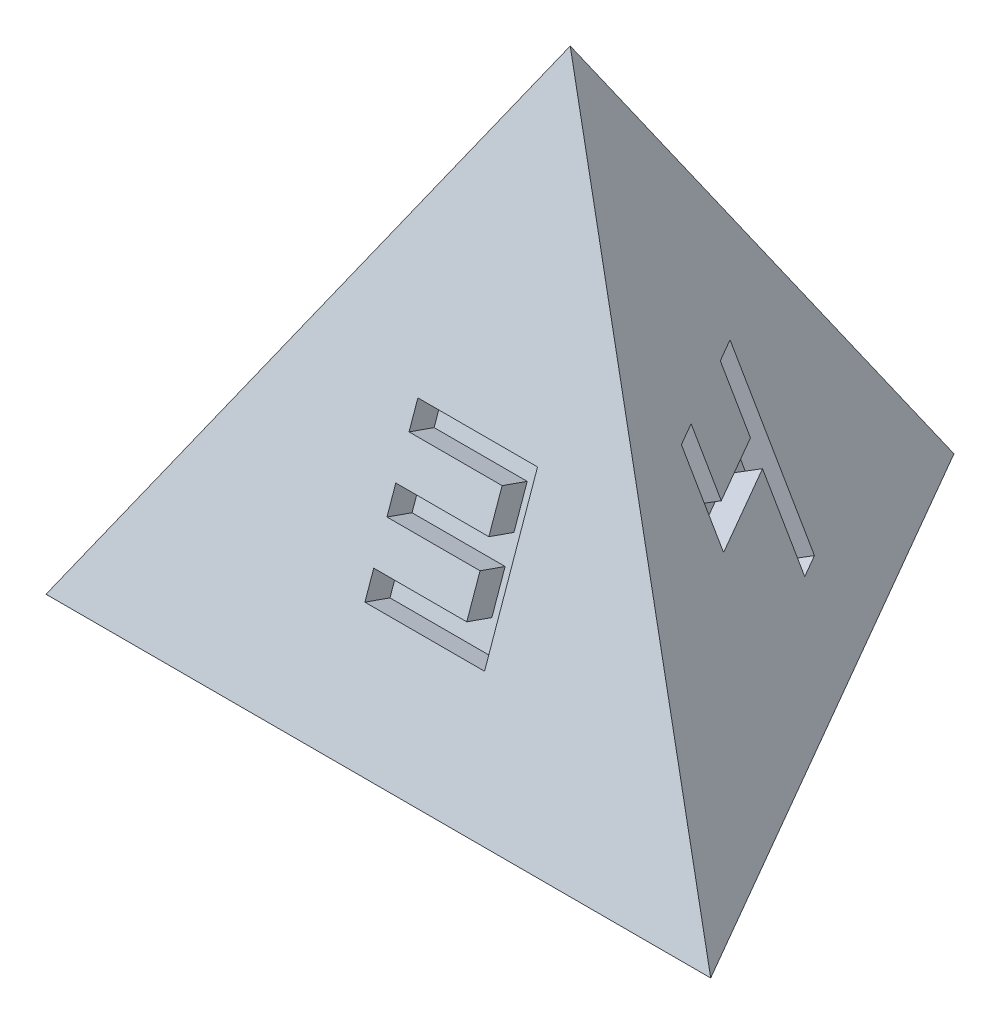
SolidWorks part; units mm, degrees
ref_plane "Front Plane" through (0, 0, 0) normal (0, 0, 1) x (1, 0, 0)
ref_plane "Top Plane" through (0, 0, 0) normal (0, 1, 0) x (1, 0, 0)
ref_plane "Right Plane" through (0, 0, 0) normal (1, 0, 0) x (0, 0, -1)
sketch "Sketch1" plane through (0, 0, 0) normal (0, 1, 0) x (1, 0, 0)
  line L1 (0, 7.3323) -> (-6.35, -3.6662)
  line L2 (-6.35, -3.6662) -> (6.35, -3.6662)
  line L3 (6.35, -3.6662) -> (0, 7.3323)
  circle A0 centre (0, 0) radius 3.6662 construction
  dimension "D1" = 12.7
ref_plane "Plane1" through (0, 10.414, 0) normal (0, 1, 0) x (1, 0, 0)
sketch "Sketch2" plane through (0, 10.414, 0) normal (0, 1, 0) x (1, 0, 0)
  point P0 (0, 0)
loft "Loft1" add profiles "Sketch2", "Sketch1"
ref_plane "Plane2" through (0, 5.334, 0) normal (0, 1, 0) x (1, 0, 0)
sketch "Sketch4" plane through (0, 1.1483, 3.2619) normal (0, 0.3321, 0.9433) x (1, 0, 0)
  line L0 (-1.016, 2.5926) -> (1.016, 2.5926)
  line L1 (1.016, 2.5926) -> (1.016, 3.8626)
  line L2 (1.016, 3.8626) -> (-1.016, 3.8626)
  line L3 (1.016, 2.5926) -> (1.016, 1.3226)
  line L4 (1.016, 1.3226) -> (-1.016, 1.3226)
  line L5 (-6.35, -1.2174) -> (6.35, -1.2174) construction
  line L6 (-6.35, -1.2174) -> (6.35, -1.2174)
  line L7 (1.27, 2.5926) -> (1.27, 4.1166)
  line L8 (1.27, 4.1166) -> (-1.016, 4.1166)
  line L9 (-1.016, 2.3386) -> (1.016, 2.3386)
  line L10 (0.762, 2.5926) -> (0.762, 1.5766)
  line L11 (0.762, 1.5766) -> (-1.016, 1.5766)
  line L12 (0.762, 2.5926) -> (0.762, 3.6086)
  line L13 (0.762, 3.6086) -> (-1.016, 3.6086)
  line L14 (-1.016, 2.8466) -> (1.016, 2.8466)
  line L15 (1.27, 2.5926) -> (1.27, 1.0686)
  line L16 (1.27, 1.0686) -> (-1.016, 1.0686)
  line L17 (-1.016, 4.1166) -> (-1.016, 3.6086)
  line L18 (-1.016, 2.8466) -> (-1.016, 2.3386)
  line L19 (-1.016, 1.5766) -> (-1.016, 1.0686)
  point P3 (0, 2.5926)
  point P10 (0, -1.2174)
  dimension "D1" = 1.27
  dimension "D2" = 2.032
  dimension "D3" = 2.54
  dimension "D4" = 0.254
  dimension "D5" = 0.254
ref_axis "Axis1" through (0, 10.414, 0) along (0, 1, 0)
extrude "Cut-Extrude1" cut sketch "Sketch4" against normal blind 0.508 contours L4 L19 L16 L15 L7 L8 L17 L2 L1 L3 | L2 L17 L13 L12 L14 L1 | L14 L12 L0 L1 | L0 L10 L9 L3 | L14 L18 L0 L12 | L0 L18 L9 L10 | L11 L19 L4 L3 L9 L10 region at (-0.127, 3.7136, 2.3588) region at (-0.127, 3.474, 2.4432) region at (0.889, 3.7136, 2.3588) region at (0.889, 3.474, 2.4432) region at (1.0541, 3.7136, 2.3588) region at (0.889, 3.3328, 2.4929) region at (0.7847, 4.1928, 2.1901)
sketch "Sketch6" plane through (2.8249, 1.1483, -1.631) normal (0.8169, 0.3321, -0.4716) x (-0.4369, -0.1776, -0.8818)
  line L0 (-1.8496, 9.6474) -> (0.2292, -1.1956) construction
  line L2 (-6.0072, -2.3913) -> (6.4656, 0) construction
  line L3 (-1.486, 2.3549) -> (0.5097, 2.7375)
  line L4 (-1.486, 2.3549) -> (-1.7729, 3.8517)
  line L5 (0.5097, 2.7375) -> (0.2227, 4.2343)
  line L6 (0.5097, 2.7375) -> (0.8923, 0.7419)
  line L7 (-1.2844, 2.6522) -> (0.4618, 2.987)
  line L8 (-1.2844, 2.6522) -> (-1.5235, 3.8995)
  line L9 (0.7591, 2.7853) -> (0.4722, 4.2821)
  line L10 (0.2602, 2.6897) -> (0.6428, 0.694)
  line L11 (-1.6876, 2.0576) -> (0.5575, 2.4881)
  line L12 (-1.6876, 2.0576) -> (-2.0224, 3.8038)
  line L13 (0.2602, 2.6897) -> (-0.0267, 4.1864)
  line L14 (0.7591, 2.7853) -> (1.1417, 0.7897)
  line L15 (-2.0224, 3.8038) -> (-1.5235, 3.8995)
  line L16 (-0.0267, 4.1864) -> (0.4722, 4.2821)
  line L17 (1.1417, 0.7897) -> (0.6428, 0.694)
  point P9 (-0.4882, 2.5462)
  dimension "D1" = 1.524
  dimension "D2" = 2.032
  dimension "D3" = 2.032
  dimension "D4" = 3.81
  dimension "D5" = 0.254
  dimension "D6" = 0.254
extrude "Cut-Extrude2" cut sketch "Sketch6" against normal blind 0.508 contours L0 L3 L4 L15 L12 L11 | L0 L7 L8 L15 L4 L3 | L7 L0 L3 L13 | L3 L0 L11 L10 | L13 L3 L5 L7 | L10 L11 L6 L3 | L16 L13 L7 L5 | L17 L14 L9 L16 L5 L6 | L17 L6 L11 L10 region at (1.8523, 3.7136, -1.5094) region at (2.0529, 3.7136, -1.162) region at (1.9254, 3.474, -1.5515) region at (2.1278, 3.474, -1.2009) region at (1.3792, 4.4324, -1.8228) region at (1.5983, 3.7136, -1.9493) region at (1.6714, 3.474, -1.9915) region at (1.5809, 3.3542, -2.2325) region at (1.9635, 2.5157, -2.1602)
sketch "Sketch7" plane through (-2.8249, 1.1483, -1.631) normal (-0.8169, 0.3321, -0.4716) x (-0.4369, 0.1776, 0.8818)
  line L0 (1.8496, 9.6474) -> (-0.2292, -1.1956) construction
  line L1 (-6.4656, 0) -> (6.0072, -2.3913) construction
  line L2 (-0.3184, 3.7353) -> (1.6773, 3.3527)
  line L3 (-0.5575, 2.4881) -> (1.4382, 2.1055)
  line L4 (-0.7966, 1.2408) -> (1.199, 0.8582)
  line L5 (-0.3184, 3.7353) -> (-0.5575, 2.4881)
  line L6 (1.4382, 2.1055) -> (1.199, 0.8582)
  line L7 (-0.8444, 0.9913) -> (1.4007, 0.5609)
  line L8 (1.7354, 2.3071) -> (1.4007, 0.5609)
  line L9 (-0.2602, 2.6897) -> (1.7354, 2.3071)
  line L10 (-0.1167, 3.4381) -> (-0.2602, 2.6897)
  line L11 (-0.1167, 3.4381) -> (1.6295, 3.1033)
  line L12 (-0.7488, 1.4902) -> (0.9974, 1.1555)
  line L13 (1.1409, 1.9038) -> (0.9974, 1.1555)
  line L14 (-0.8548, 2.2864) -> (1.1409, 1.9038)
  line L15 (-0.52, 4.0326) -> (-0.8548, 2.2864)
  line L16 (-0.52, 4.0326) -> (1.7251, 3.6022)
  line L17 (1.7251, 3.6022) -> (1.6295, 3.1033)
  line L18 (-0.7488, 1.4902) -> (-0.8444, 0.9913)
  point P8 (0.6795, 3.544)
  point P11 (0.4403, 2.2968)
  point P14 (0.2012, 1.0495)
  dimension "D1" = 2.032
  dimension "D2" = 1.27
  dimension "D3" = 1.27
  dimension "D4" = 2.286
  dimension "D5" = 0.254
  dimension "D6" = 0.254
extrude "Cut-Extrude3" cut sketch "Sketch7" against normal blind 0.508 contours L0 L2 L5 L3 L9 L10 L11 | L0 L16 L15 L14 L3 L5 L2 | L16 L0 L2 L17 | L2 L0 L11 L17 | L9 L0 L3 L6 L4 L7 L8 | L3 L0 L14 L13 L12 L4 L6 | L0 L12 L18 L4 | L0 L4 L18 L7 region at (-2.0046, 4.6719, -0.5708) region at (-1.7379, 4.6719, -1.0327) region at (-2.0777, 4.4324, -0.613) region at (-1.8142, 4.4324, -1.0693) region at (-2.4041, 3.5699, -0.6548) region at (-2.1984, 3.2344, -1.2473) region at (-2.2271, 2.2761, -1.8724) region at (-2.3001, 2.0365, -1.9146)
sketch "Sketch8" plane through (0, 0, 0) normal (0, -1, 0) x (1, 0, 0)
  line L1 (-6.35, 3.6662) -> (6.35, 3.6662) construction
  line L7 (0, 3.6662) -> (0, -7.3323) construction
  line L8 (1.016, 1.524) -> (-1.016, 1.524)
  line L9 (1.016, 1.524) -> (1.016, -1.524)
  line L10 (-1.016, 0) -> (-1.016, 1.524)
  line L11 (1.016, -1.524) -> (-1.016, -1.524)
  line L12 (-0.762, 0.254) -> (0.762, 0.254)
  line L13 (-0.762, 0.254) -> (-0.762, 1.27)
  line L14 (0.762, 1.27) -> (-0.762, 1.27)
  line L15 (0.762, 1.27) -> (0.762, -1.27)
  line L31 (0.762, -1.27) -> (-1.016, -1.27)
  line L32 (-1.27, -0.254) -> (0.762, -0.254)
  line L33 (-1.27, -0.254) -> (-1.27, 1.778)
  line L34 (1.27, 1.778) -> (-1.27, 1.778)
  line L35 (1.27, 1.778) -> (1.27, -1.778)
  line L36 (1.27, -1.778) -> (-1.016, -1.778)
  line L37 (-1.016, -1.778) -> (-1.016, -1.27)
  line L38 (-1.27, 3.048) -> (-1.27, 2.54)
  line L39 (1.27, 3.048) -> (1.27, 2.54)
  line L40 (1.27, 3.048) -> (-1.27, 3.048)
  line L41 (1.27, 2.54) -> (-1.27, 2.54)
  line L42 (1.27, 2.794) -> (-1.27, 2.794)
  line L43 (-1.016, 0) -> (0.762, 0)
  point P4 (0, 0)
  point P8 (0, 2.794)
  point P47 (0, 1.524)
  dimension "D1" = 5.08
  dimension "D2" = 5.334
  dimension "D3" = 5.588
  dimension "D4" = 0.6182
  dimension "D5" = 0.8722
  dimension "D6" = 1.8882
  dimension "D7" = 3.4122
extrude "Cut-Extrude4" cut sketch "Sketch8" against normal blind 0.508 and the other way through all contours L7 L31 L37 L11 | L34 L7 L8 L9 L11 L36 L35 | L7 L11 L37 L36 | L8 L7 L14 L15 L31 L11 L9 | L43 L7 L32 L15 | L7 L34 L33 L32 L43 L10 L8 | L7 L8 L10 L43 L12 L13 L14 | L12 L7 L43 L15 | L41 L38 L40 L39 region at (0.635, 0, 1.7402) region at (-0.024, 0, 1.651) region at (0.508, 0, 1.4919) region at (-0.0183, 0, 1.397) region at (0.381, 0, 0.127) region at (-0.508, 0, -1.651) region at (0.381, 0, -0.127) region at (-0.508, 0, -1.397)
